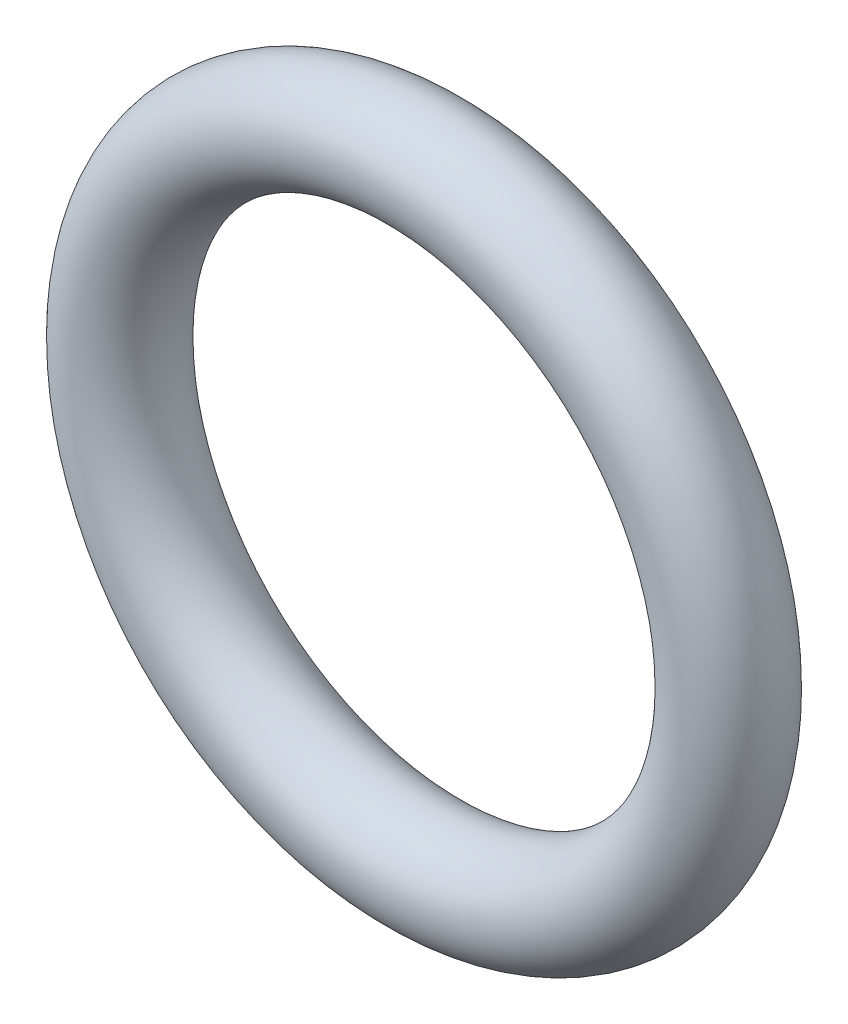
SolidWorks part; units mm, degrees
ref_plane "Front" through (0, 0, 0) normal (0, 0, 1) x (1, 0, 0)
ref_plane "Top" through (0, 0, 0) normal (0, 1, 0) x (1, 0, 0)
ref_plane "Right" through (0, 0, 0) normal (1, 0, 0) x (0, 0, -1)
sketch "Sketch1" plane through (0, 0, 0) normal (1, 0, 0) x (0, -1, 0)
  line L0 (0, -0.9144) -> (0, 0.9144) construction
  line L2 (-6.9151, 0) -> (6.9151, 0) construction
  line L3 (-4.4577, 0) -> (4.4577, 0) construction
  circle A0 centre (5.3721, 0) radius 0.9144
  point P9 (4.4577, 0)
  point P10 (6.2865, 0)
  point P13 (5.3721, 0.9144)
  point P14 (5.3721, -0.9144)
  dimension "Width" = 1.8288
  dimension "ID" = 8.9154
revolve "Revolve1" add sketch "Sketch1" angle 360 about L0
ref_axis "Axis1" through (0, 0, -1.0058) along (0, 0, 1)
